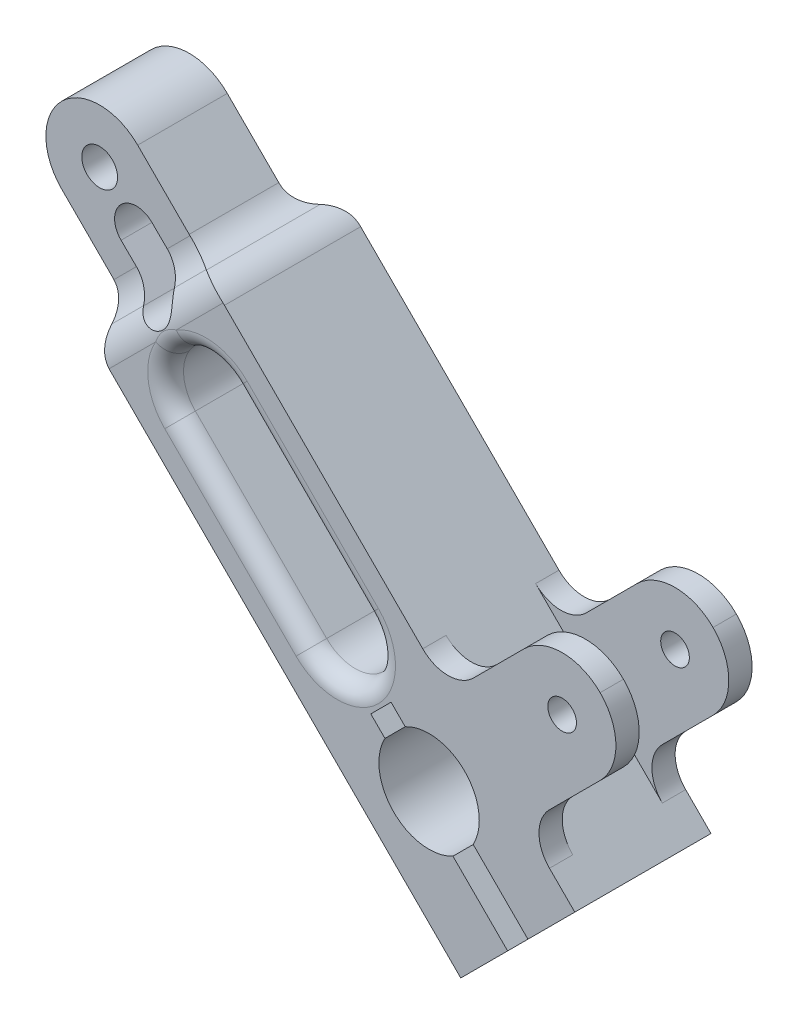
SolidWorks part; units mm, degrees
ref_plane "Front Plane" through (0, 0, 0) normal (0, 0, 1) x (1, 0, 0)
ref_plane "Top Plane" through (0, 0, 0) normal (0, 1, 0) x (1, 0, 0)
ref_plane "Right Plane" through (0, 0, 0) normal (1, 0, 0) x (0, 0, -1)
sketch "Sketch2" plane through (0, 0, 0) normal (0, 0, 1) x (1, 0, 0)
  line L0 (0, 0) -> (-234.0257, 0) construction
  line L1 (0, 0) -> (132.15, 132.15) construction
  line L2 (0, 0) -> (130.2279, -130.2279) construction
  line L3 (-10.6066, -10.6066) -> (10.6066, 10.6066) construction
  line L4 (-10.6066, -10.6066) -> (21.2132, -42.4264) construction
  line L5 (21.2132, -42.4264) -> (42.4264, -21.2132) construction
  line L6 (42.4264, -21.2132) -> (10.6066, 10.6066) construction
  line L7 (0, -21.2132) -> (21.2132, 0)
  line L9 (21.2132, 0) -> (53.033, -31.8198)
  line L10 (0, -21.2132) -> (31.8198, -53.033)
  line L11 (31.8198, -53.033) -> (26.5165, -58.3363)
  line L12 (114.318, -146.1378) -> (26.5165, -58.3363)
  line L13 (53.033, -31.8198) -> (58.3363, -26.5165)
  line L14 (124.9246, -93.1047) -> (58.3363, -26.5165)
  line L15 (146.1378, -114.318) -> (177.9576, -82.4981)
  line L16 (177.9576, -82.4981) -> (156.7444, -61.2849)
  line L17 (156.7444, -61.2849) -> (124.9246, -93.1047)
  line L18 (167.351, -71.8915) -> (119.6213, -119.6213) construction
  line L19 (146.1378, -114.318) -> (160.2799, -128.4601)
  line L20 (114.318, -146.1378) -> (128.4601, -160.2799)
  line L21 (160.2799, -128.4601) -> (147.1984, -141.5416)
  line L22 (109.0147, -103.3578) -> (112.9628, -107.306)
  line L23 (103.3578, -109.0147) -> (109.0147, -103.3578)
  line L24 (103.3578, -109.0147) -> (107.306, -112.9628)
  line L25 (131.9365, -126.2797) -> (147.1984, -141.5416)
  line L26 (126.2797, -131.9365) -> (141.5416, -147.1984)
  line L27 (141.5416, -147.1984) -> (128.4601, -160.2799)
  line L28 (31.8198, -53.033) -> (53.033, -31.8198)
  line L29 (124.9246, -93.1047) -> (146.1378, -114.318)
  circle A0 centre (21.2132, -21.2132) radius 5
  circle A1 centre (156.7444, -82.4981) radius 4
  arc A2 (107.306, -112.9628) -> (126.2797, -131.9365) centre (119.6213, -119.6213) ccw
  arc A3 (131.9365, -126.2797) -> (112.9628, -107.306) centre (119.6213, -119.6213) ccw
  point P8 (0, 0)
  point P15 (10.6066, -10.6066)
  point P18 (130.2279, -130.2279)
  point P35 (122.4497, -116.7928)
  point P40 (106.1862, -106.1862)
  dimension "D4" = 10
  dimension "D5" = 15
  dimension "D12" = 8
  dimension "D13" = 15
  dimension "D14" = 28
  dimension "D1" = 184.17
  dimension "D2" = 30
  dimension "D3" = 45
  dimension "D6" = 15
  dimension "D7" = 30
  dimension "D8" = 45
  dimension "D9" = 45
  dimension "D10" = 45
  dimension "D11" = 30
  dimension "D15" = 20
  dimension "D17" = 19
extrude "Boss-Extrude1" add sketch "Sketch2" along normal blind 38 contours A3 L25 L21 L19 L29 L14 L13 L28 L11 L12 L20 L27 L26 A2 L24 L23 L22 region at (89.1363, -89.1363, 0)
extrude "Boss-Extrude2" add sketch "Sketch2<3>" along normal blind 6.5 contours L17 L29 L15 L16 A1 region at (151.236, -88.0065, 0)
sketch "Sketch2<3>" plane through (0, 0, 0) normal (0, 0, 1) x (1, 0, 0) same geometry as "Sketch2"
fillet "Fillet1" radius 15 2 edges at (177.9576, -82.4981, 3.25) (156.7444, -61.2849, 3.25)
ref_plane "Plane1" through (0, 0, 19) normal (0, 0, -1) x (-1, 0, 0)
mirror "Mirror1" about plane through (0, 0, 19) normal (0, 0, -1) of "Boss-Extrude2", "Fillet1"
sketch "Sketch3" plane through (42.4264, -42.4264, 0) normal (-0.7071, 0.7071, 0) x (0, 0, 1)
  line L0 (19, 73.5699) -> (19, -73.5699) construction
  line L1 (6.5, 15) -> (31.5, 15)
  line L2 (6.5, 15) -> (6.5, -15)
  line L3 (6.5, -15) -> (31.5, -15)
  line L4 (31.5, 15) -> (31.5, -15)
  line L5 (6.5, 15) -> (31.5, -15) construction
  line L6 (6.5, -15) -> (31.5, 15) construction
  point P0 (19, 0)
  dimension "D1" = 30
  dimension "D2" = 25
extrude "Boss-Extrude3" add sketch "Sketch3" along normal blind 45
sketch "Sketch4" plane through (0, 0, 31.5) normal (0, 0, 1) x (1, 0, 0)
  line L0 (10.6066, -10.6066) -> (31.8198, -31.8198) construction
  line L1 (0, -21.2132) -> (21.2132, 0) construction
  circle A0 centre (21.2132, -21.2132) radius 5
  dimension "D1" = 10
  dimension "D2" = 15
extrude "Cut-Extrude1" cut sketch "Sketch4" against normal through all
fillet "Fillet2" radius 15 2 edges at (21.2132, 0, 19) (0, -21.2132, 19)
sketch "Sketch5" plane through (144.37, -144.37, 0) normal (0.7071, -0.7071, 0) x (0, 0, -1)
  line L0 (-38, -13.25) -> (0, -13.25) construction
  line L1 (-38, -4) -> (-38, -22.5) construction
  line L2 (0, -4) -> (0, -22.5) construction
  circle A0 centre (-27, -13.25) radius 4
  circle A1 centre (-13, -13.25) radius 4
  dimension "D1" = 8
  dimension "D2" = 8
  dimension "D3" = 14
  dimension "D4" = 11
extrude "Cut-Extrude2" cut sketch "Sketch5" against normal blind 10
fillet "Fillet3" radius 10 8 edges at (42.4264, -42.4264, 31.5) (31.8198, -53.033, 19) (53.033, -31.8198, 19) (42.4264, -42.4264, 6.5) (124.9246, -93.1047, 34.75) (124.9246, -93.1047, 3.25) (146.1378, -114.318, 34.75) (146.1378, -114.318, 3.25)
fillet "Fillet4" radius 10 4 edges at (42.4264, -42.4264, 0) (26.5165, -58.3363, 19) (42.4264, -42.4264, 38) (58.3363, -26.5165, 19)
sketch "Sketch6" plane through (0, 0, 0) normal (0, 0, -1) x (-1, 0, 0)
  line L0 (-46.2369, -46.2369) -> (-106.1862, -106.1862) construction
  line L1 (-30.3374, -62.1364) -> (-62.1364, -30.3374) construction
  line L2 (-103.3578, -109.0147) -> (-109.0147, -103.3578) construction
  line L3 (-57.366, -57.366) -> (-93.9989, -93.9989) construction
  line L4 (-49.4111, -65.321) -> (-86.044, -101.9539)
  line L5 (-65.321, -49.4111) -> (-101.9539, -86.044)
  line L6 (-46.2369, -46.2369) -> (-7.1246, -7.4244) construction
  line L7 (-41.0197, -41.0197) -> (-31.4603, -31.5736) construction
  line L8 (-54.1799, -27.8596) -> (-27.8596, -54.1799) construction
  line L9 (-45.2948, -36.6935) -> (-35.7353, -27.2473)
  line L10 (-36.7447, -45.346) -> (-27.1853, -35.8999)
  arc A0 (-49.4111, -65.321) -> (-65.321, -49.4111) centre (-57.366, -57.366) ccw
  arc A1 (-101.9539, -86.044) -> (-86.044, -101.9539) centre (-93.9989, -93.9989) ccw
  arc A2 (-45.2948, -36.6935) -> (-36.7447, -45.346) centre (-41.0197, -41.0197) ccw
  arc A3 (-27.1853, -35.8999) -> (-35.7353, -27.2473) centre (-31.4603, -31.5736) ccw
  point P8 (-75.6825, -75.6825)
  point P18 (-36.24, -36.2967)
  point P23 (-31.4603, -31.5736)
  point P24 (-41.0197, -41.0197)
  dimension "D1" = 11.25
extrude "Cut-Extrude3" cut sketch "Sketch6" against normal through all
fillet "Fillet5" radius 5 8 edges at (49.4111, -49.4111, 0) (67.7275, -83.6374, 0) (101.9539, -101.9539, 0) (101.9539, -101.9539, 38) (67.7275, -83.6374, 38) (49.4111, -49.4111, 38) (83.6374, -67.7275, 0) (83.6374, -67.7275, 38)
